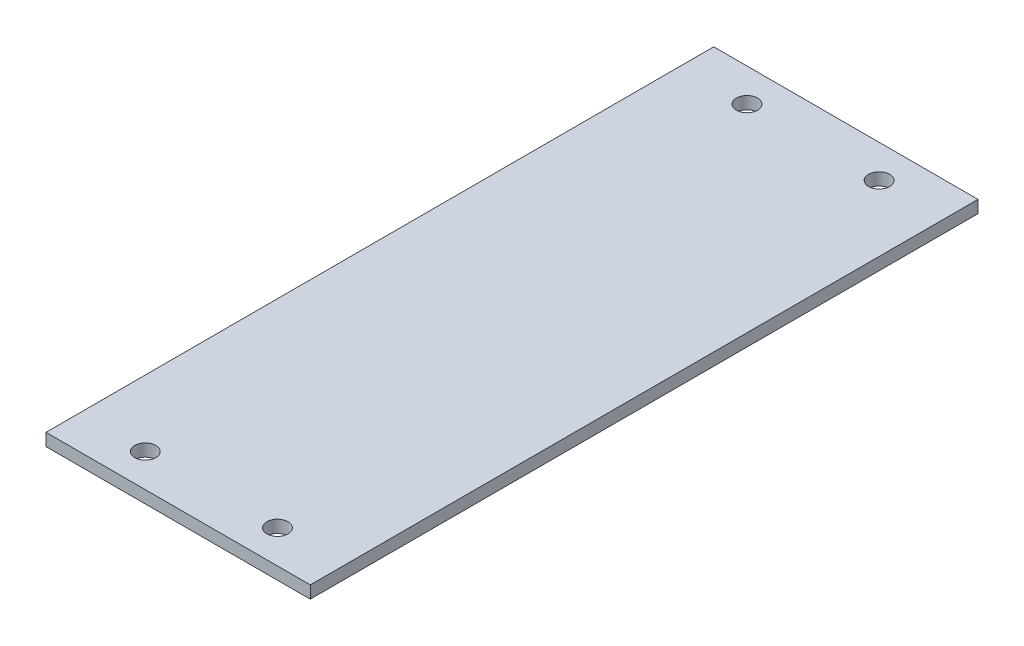
SolidWorks part; units mm, degrees
material "Balsa"
ref_plane "Front Plane" through (0, 0, 0) normal (0, 0, 1) x (1, 0, 0)
ref_plane "Top Plane" through (0, 0, 0) normal (0, 1, 0) x (1, 0, 0)
ref_plane "Right Plane" through (0, 0, 0) normal (1, 0, 0) x (0, 0, -1)
sketch "Sketch1" plane through (0, 0, 0) normal (0, 1, 0) x (1, 0, 0)
  line L0 (-152.4, 304.8) -> (152.4, 304.8) construction
  line L1 (152.4, 304.8) -> (152.4, -304.8) construction
  line L2 (0, 304.8) -> (0, 0) construction
  line L3 (0, 0) -> (152.4, 0) construction
  dimension "Width" = 304.8
  dimension "Length" = 609.6
sketch "Sketch2" plane through (0, 0, 0) normal (1, 0, 0) x (0, 0, -1)
  line L0 (304.8, 0) -> (304.8, -9.525) construction
  dimension "Thk" = 9.525
sketch "Sketch3" plane through (0, 0, 0) normal (0, 1, 0) x (1, 0, 0)
  line L1 (-152.4, 304.8) -> (152.4, 304.8)
  line L2 (-152.4, 304.8) -> (-152.4, -304.8)
  line L3 (-152.4, -304.8) -> (152.4, -304.8)
  line L4 (152.4, 304.8) -> (152.4, -304.8)
extrude "Boss-Extrude1" add sketch "Sketch3" against normal up to vertex (9.525 mm away) up to point (0, -9.525, -304.8)
sketch "Sketch4" plane through (0, 0, 0) normal (0, 1, 0) x (1, 0, 0)
  line L0 (152.4, -304.8) -> (152.4, 304.8) construction
  line L1 (-152.4, 304.8) -> (152.4, 304.8)
  line L2 (-152.4, 304.8) -> (-152.4, 208.661)
  line L3 (-120.245, 208.661) -> (120.245, 208.661)
  line L4 (152.4, 304.8) -> (152.4, 208.661)
  line L5 (-152.4, -304.8) -> (152.4, -304.8) construction
  line L6 (0, 0) -> (0, 208.661) construction
  line L8 (-152.4, 208.661) -> (-152.4, -304.8)
  line L9 (-152.4, -304.8) -> (-120.245, -304.8)
  line L10 (-120.245, 208.661) -> (-120.245, -304.8)
  line L11 (152.4, 208.661) -> (152.4, -304.8)
  line L12 (120.245, 208.661) -> (120.245, -304.8)
  line L13 (152.4, -304.8) -> (120.245, -304.8)
  dimension "D1" = 513.461
  dimension "D2" = 32.155
  dimension "D3" = 32.155
extrude "Cut-Extrude1" cut sketch "Sketch4" against normal blind 15.24 contours L2 L8 L9 L10 L3 L12 L13 L11 L4 L1
sketch "Sketch5" plane through (0, 0, 0) normal (0, 1, 0) x (1, 0, 0)
  line L1 (-50.8, -109.22) -> (50.8, -109.22)
  line L2 (-57.15, -102.87) -> (-57.15, -20.32)
  line L3 (-50.8, -13.97) -> (50.8, -13.97)
  line L4 (57.15, -102.87) -> (57.15, -20.32)
  line L5 (-57.15, -109.22) -> (57.15, -13.97) construction
  line L6 (-57.15, -13.97) -> (57.15, -109.22) construction
  arc A0 (-50.8, -109.22) -> (-57.15, -102.87) centre (-50.8, -102.87) cw
  arc A1 (50.8, -109.22) -> (57.15, -102.87) centre (50.8, -102.87) ccw
  arc A2 (50.8, -13.97) -> (57.15, -20.32) centre (50.8, -20.32) cw
  arc A3 (-57.15, -20.32) -> (-50.8, -13.97) centre (-50.8, -20.32) cw
  point P0 (0, -61.595)
  dimension "D4" = 6.35
  dimension "D1" = 95.25
  dimension "D2" = 61.595
  dimension "D3" = 114.3
extrude "Cut-Extrude2" [suppressed] cut sketch "Sketch5" against normal blind 12.7
sketch "Sketch9" plane through (0, -9.525, 0) normal (0, -1, 0) x (-1, 0, 0)
  line L0 (101.442, 208.661) -> (-101.7753, 208.661) construction
  line L1 (120.245, 208.661) -> (-120.245, 208.661) construction
  line L2 (-0.1667, 208.661) -> (-0.1667, 141.8706) construction
  line L3 (-101.7753, 208.661) -> (-101.6, -304.8) construction
  line L4 (120.245, -304.8) -> (-120.245, -304.8) construction
  line L5 (-101.6, -304.8) -> (-101.6877, -48.0695) construction
  line L6 (-101.6877, -48.0695) -> (101.6, -48.0695) construction
  line L7 (50.6333, 208.661) -> (-0.1667, 208.661) construction
  line L8 (-0.1667, 208.661) -> (-50.9667, 208.661) construction
  line L9 (50.6333, 208.661) -> (50.6333, 183.261) construction
  line L10 (50.6333, 183.261) -> (-50.9667, 183.261) construction
  line L11 (-50.9667, 183.261) -> (-50.9667, 208.661) construction
  line L12 (-0.1667, 141.8706) -> (-3.0721, -304.8) construction
  circle A0 centre (-50.9667, 183.261) radius 8.128
  circle A2 centre (50.6333, 183.261) radius 8.128
  circle A5 centre (50.6333, -279.4) radius 8.128
  circle A6 centre (-50.9667, -279.4) radius 8.128
  dimension "D3" = 25.4
  dimension "D1" = 16.256
  dimension "D2" = 50.8
  dimension "D4" = 50.8
extrude "Cut-Extrude3" cut sketch "Sketch9" against normal through all
sketch "Sketch10" plane through (0, -9.525, 0) normal (0, -1, 0) x (1, 0, 0)
  line L0 (-120.245, -208.661) -> (120.245, -208.661) construction
  line L1 (-101.6, -208.661) -> (101.6, -208.661)
  line L2 (-101.6, -208.661) -> (-101.6, 304.8)
  line L3 (-101.6, 304.8) -> (101.6, 304.8)
  line L4 (101.6, -208.661) -> (101.6, 304.8)
  line L5 (-120.245, 304.8) -> (120.245, 304.8) construction
  line L6 (-101.6, 0) -> (101.6, 0) construction
  line L8 (-120.245, -208.661) -> (120.245, -208.661)
  line L9 (-120.245, -208.661) -> (-120.245, 304.8)
  line L10 (-120.245, 304.8) -> (120.245, 304.8)
  line L11 (120.245, -208.661) -> (120.245, 304.8)
  line M6 (-120.245, -208.661) -> (120.245, -208.661)
  line M7 (120.245, -208.661) -> (120.245, 304.8)
  line M8 (120.245, 304.8) -> (-120.245, 304.8)
  line M9 (-120.245, 304.8) -> (-120.245, -208.661)
  dimension "D1" = 203.2
extrude "Cut-Extrude4" cut sketch "Sketch10" against normal blind 41.656 contours L4 M6 M7 M8 | L2 M6 M8 M9 region at (-110.9225, -9.525, 48.0695) region at (110.9225, -9.525, 48.0695)
